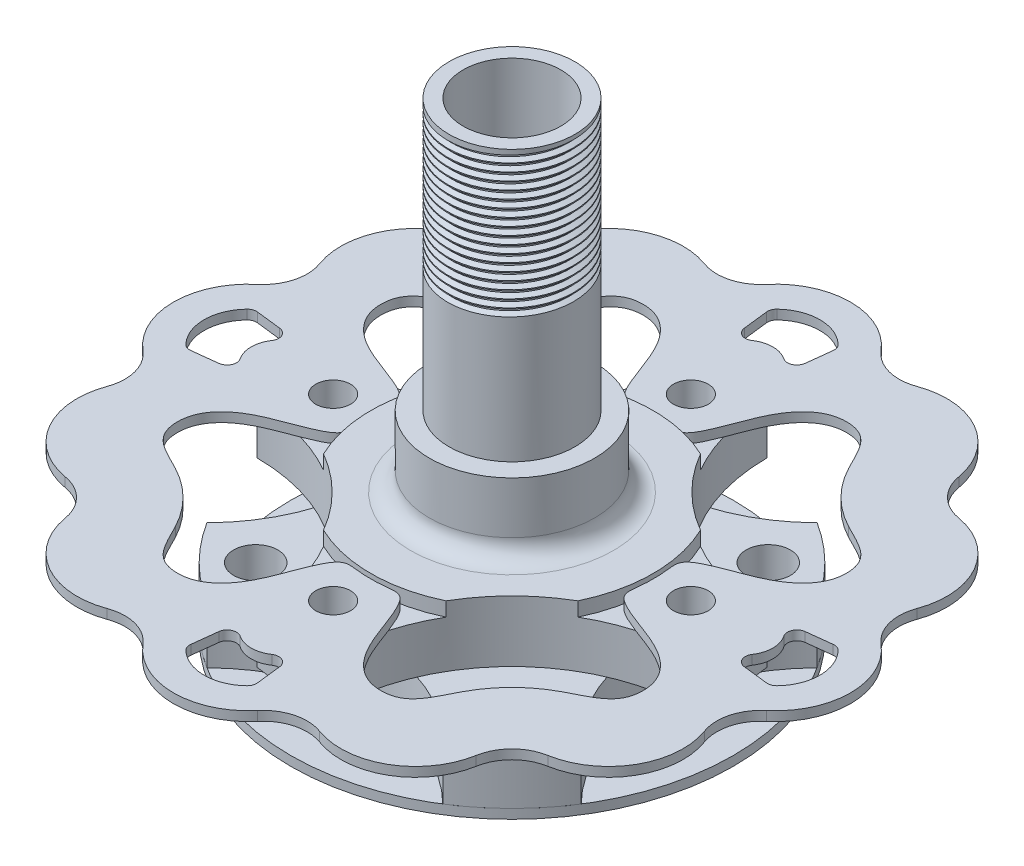
SolidWorks part; units mm, degrees
other "Camera1"
ref_plane "Front Plane" through (0, 0, 0) normal (0, 0, 1) x (1, 0, 0)
ref_plane "Top Plane" through (0, 0, 0) normal (0, 1, 0) x (1, 0, 0)
ref_plane "Right Plane" through (0, 0, 0) normal (1, 0, 0) x (0, 0, -1)
sketch "Sketch1" plane through (0, 0, 0) normal (0, 1, 0) x (1, 0, 0)
  line L0 (-91.3384, 0) -> (0, 0) construction
  line L1 (-79.1014, 45.6692) -> (0, 0) construction
  line L2 (-45.6692, 79.1014) -> (0, 0) construction
  line L3 (0, 91.3384) -> (0, 0) construction
  line L4 (-58.7488, 58.7488) -> (0, 0) construction
  line L5 (-77.6512, 8.9971) -> (-70.888, 8.2135)
  line L9 (0, 91.3384) -> (0, 0) construction
  line L10 (-8.9971, 77.6512) -> (-8.2135, 70.888)
  line L11 (8.9971, 77.6512) -> (8.2135, 70.888)
  line L12 (77.6512, 8.9971) -> (70.888, 8.2135)
  line L13 (0, 91.3384) -> (0, 0) construction
  line L16 (45.6692, 79.1014) -> (0, 0) construction
  line L17 (79.1014, 45.6692) -> (0, 0) construction
  line L18 (91.3384, 0) -> (0, 0) construction
  line L19 (58.7488, 58.7488) -> (0, 0) construction
  line L20 (91.3384, 0) -> (0, 0) construction
  line L23 (0, 91.3384) -> (0, 0) construction
  line L24 (77.6512, -8.9971) -> (70.888, -8.2135)
  line L25 (8.9971, -77.6512) -> (8.2135, -70.888)
  line L26 (-91.3384, 0) -> (0, 0) construction
  line L27 (91.3384, 0) -> (0, 0) construction
  line L28 (77.6512, -8.9971) -> (70.888, -8.2135) [skipped]
  line L30 (-8.9971, -77.6512) -> (-8.2135, -70.888) [skipped]
  line L32 (79.1014, -45.6692) -> (0, 0) construction
  line L33 (45.6692, -79.1014) -> (0, 0) construction
  line L34 (0, -91.3384) -> (0, 0) construction
  line L35 (58.7488, -58.7488) -> (0, 0) construction
  line L36 (0, -91.3384) -> (0, 0) construction
  line L37 (-45.6692, -79.1014) -> (0, 0) construction
  line L38 (-79.1014, -45.6692) -> (0, 0) construction
  line L39 (-58.7488, -58.7488) -> (0, 0) construction
  line L40 (8.9971, 77.6512) -> (8.2135, 70.888) [skipped]
  line L41 (45.6692, 79.1014) -> (0, 0) construction
  line L42 (79.1014, 45.6692) -> (0, 0) construction
  line L43 (58.7488, 58.7488) -> (0, 0) construction
  line L45 (91.3384, 0) -> (0, 0) construction
  line L46 (91.3384, 0) -> (0, 0) construction
  line L47 (79.1014, -45.6692) -> (0, 0) construction
  line L48 (45.6692, -79.1014) -> (0, 0) construction
  line L49 (0, -91.3384) -> (0, 0) construction
  line L50 (58.7488, -58.7488) -> (0, 0) construction
  line L51 (0, -91.3384) -> (0, 0) construction
  line L52 (91.3384, 0) -> (0, 0) construction
  line L53 (-8.9971, -77.6512) -> (-8.2135, -70.888)
  line L54 (-77.6512, -8.9971) -> (-70.888, -8.2135)
  line L55 (0, -91.3384) -> (0, 0) construction
  line L56 (-45.6692, -79.1014) -> (0, 0) construction
  line L57 (-79.1014, -45.6692) -> (0, 0) construction
  line L58 (-91.3384, 0) -> (0, 0) construction
  line L59 (-58.7488, -58.7488) -> (0, 0) construction
  line L60 (-91.3384, 0) -> (0, 0) construction
  line L61 (0, -91.3384) -> (0, 0) construction
  arc A0 (-83.0834, 0) -> (0, 83.0834) centre (0, 0) cw construction
  arc A1 (-91.3384, 0) -> (0, 91.3384) centre (0, 0) cw construction
  arc A2 (-91.3384, 0) -> (-84.1072, 15.4663) centre (-71.1829, 0) cw
  arc A3 (-84.1072, 15.4663) -> (-80.5721, 28.6594) centre (-91.7199, 24.5763) ccw
  arc A4 (-80.5721, 28.6594) -> (-65.1058, 55.4478) centre (-61.6462, 35.5915) cw
  arc A5 (-65.1058, 55.4478) -> (-55.4478, 65.1058) centre (-67.1436, 67.1436) ccw
  arc A6 (-55.4478, 65.1058) -> (-28.6594, 80.5721) centre (-35.5915, 61.6462) cw
  arc A7 (-28.6594, 80.5721) -> (-15.4663, 84.1072) centre (-24.5763, 91.7199) ccw
  arc A8 (-15.4663, 84.1072) -> (0, 91.3384) centre (0, 71.1829) cw
  arc A9 (-61.618, 35.4294) -> (-35.4294, 61.618) centre (-67.1436, 67.1436) ccw
  arc A10 (-38.1, 0) -> (-37.7962, 4.8015) centre (0, 0) cw
  arc A11 (-83.0834, 0) -> (-79.7781, 8.2307) centre (-71.1829, 0) cw
  arc A12 (-69.0761, 4.2678) -> (-70.3834, 0) centre (-62.7634, 0) ccw
  arc A14 (-83.0834, 0) -> (-78.8139, 9.1318) centre (-71.1829, 0) cw construction
  arc A15 (-77.6512, 8.9971) -> (-79.7781, 8.2307) centre (-77.9435, 6.474) ccw
  arc A16 (-69.0761, 4.2678) -> (-70.888, 8.2135) centre (-71.1804, 5.6904) ccw
  circle A17 centre (-48.26, 0) radius 4.699
  arc A29 (0, 38.1) -> (-4.8015, 37.7962) centre (0, 0) ccw
  arc A30 (-4.2678, 69.0761) -> (0, 70.3834) centre (0, 62.7634) cw
  arc A36 (-4.2678, 69.0761) -> (-8.2135, 70.888) centre (-5.6904, 71.1804) cw
  arc A41 (-8.9971, 77.6512) -> (-8.2307, 79.7781) centre (-6.474, 77.9435) cw
  arc A42 (0, 83.0834) -> (-8.2307, 79.7781) centre (0, 71.1829) ccw
  arc A50 (0, 91.3384) -> (15.4663, 84.1072) centre (0, 71.1829) cw
  arc A51 (15.4663, 84.1072) -> (28.6594, 80.5721) centre (24.5763, 91.7199) ccw
  arc A57 (28.6594, 80.5721) -> (55.4478, 65.1058) centre (35.5915, 61.6462) cw
  arc A62 (55.4478, 65.1058) -> (65.1058, 55.4478) centre (67.1436, 67.1436) ccw
  arc A63 (65.1058, 55.4478) -> (80.5721, 28.6594) centre (61.6462, 35.5915) cw
  arc A71 (80.5721, 28.6594) -> (84.1072, 15.4663) centre (91.7199, 24.5763) ccw
  arc A72 (84.1072, 15.4663) -> (91.3384, 0) centre (71.1829, 0) cw
  arc A78 (-38.1, 0) -> (-37.7962, -4.8015) centre (0, 0) ccw
  arc A81 (-69.0761, -4.2678) -> (-70.3834, 0) centre (-62.7634, 0) cw
  arc A83 (35.4294, 61.618) -> (61.618, 35.4294) centre (67.1436, 67.1436) ccw
  arc A84 (0, 38.1) -> (4.8015, 37.7962) centre (0, 0) cw
  arc A85 (91.3384, 0) -> (84.1072, -15.4663) centre (71.1829, 0) cw [skipped]
  arc A86 (84.1072, -15.4663) -> (80.5721, -28.6594) centre (91.7199, -24.5763) ccw [skipped]
  arc A87 (80.5721, -28.6594) -> (65.1058, -55.4478) centre (61.6462, -35.5915) cw [skipped]
  arc A88 (65.1058, -55.4478) -> (55.4478, -65.1058) centre (67.1436, -67.1436) ccw [skipped]
  arc A89 (55.4478, -65.1058) -> (28.6594, -80.5721) centre (35.5915, -61.6462) cw [skipped]
  arc A90 (28.6594, -80.5721) -> (15.4663, -84.1072) centre (24.5763, -91.7199) ccw [skipped]
  arc A91 (15.4663, -84.1072) -> (0, -91.3384) centre (0, -71.1829) cw [skipped]
  arc A92 (61.618, -35.4294) -> (35.4294, -61.618) centre (67.1436, -67.1436) ccw [skipped]
  arc A93 (83.0834, 0) -> (79.7781, -8.2307) centre (71.1829, 0) cw [skipped]
  arc A95 (77.6512, -8.9971) -> (79.7781, -8.2307) centre (77.9435, -6.474) ccw [skipped]
  arc A96 (69.0761, -4.2678) -> (70.888, -8.2135) centre (71.1804, -5.6904) ccw [skipped]
  arc A102 (0, -91.3384) -> (-15.4663, -84.1072) centre (0, -71.1829) cw [skipped]
  arc A103 (-15.4663, -84.1072) -> (-28.6594, -80.5721) centre (-24.5763, -91.7199) ccw [skipped]
  arc A104 (-28.6594, -80.5721) -> (-55.4478, -65.1058) centre (-35.5915, -61.6462) cw [skipped]
  arc A105 (-55.4478, -65.1058) -> (-65.1058, -55.4478) centre (-67.1436, -67.1436) ccw [skipped]
  arc A106 (-65.1058, -55.4478) -> (-80.5721, -28.6594) centre (-61.6462, -35.5915) cw [skipped]
  arc A107 (-80.5721, -28.6594) -> (-84.1072, -15.4663) centre (-91.7199, -24.5763) ccw [skipped]
  arc A108 (-84.1072, -15.4663) -> (-91.3384, 0) centre (-71.1829, 0) cw [skipped]
  arc A109 (-35.4294, -61.618) -> (-61.618, -35.4294) centre (-67.1436, -67.1436) ccw [skipped]
  arc A110 (0, -38.1) -> (-4.8015, -37.7962) centre (0, 0) cw [skipped]
  arc A111 (0, -83.0834) -> (-8.2307, -79.7781) centre (0, -71.1829) cw [skipped]
  arc A112 (-4.2678, -69.0761) -> (0, -70.3834) centre (0, -62.7634) ccw [skipped]
  arc A114 (-8.9971, -77.6512) -> (-8.2307, -79.7781) centre (-6.474, -77.9435) ccw [skipped]
  arc A115 (-4.2678, -69.0761) -> (-8.2135, -70.888) centre (-5.6904, -71.1804) ccw [skipped]
  arc A119 (83.0834, 0) -> (0, -83.0834) centre (0, 0) cw construction
  arc A120 (91.3384, 0) -> (0, -91.3384) centre (0, 0) cw construction
  arc A121 (0, -83.0834) -> (-83.0834, 0) centre (0, 0) cw construction
  arc A122 (0, -91.3384) -> (-91.3384, 0) centre (0, 0) cw construction
  arc A123 (0, 91.3384) -> (15.4663, 84.1072) centre (0, 71.1829) cw [skipped]
  arc A124 (15.4663, 84.1072) -> (28.6594, 80.5721) centre (24.5763, 91.7199) ccw [skipped]
  arc A125 (28.6594, 80.5721) -> (55.4478, 65.1058) centre (35.5915, 61.6462) cw [skipped]
  arc A126 (55.4478, 65.1058) -> (65.1058, 55.4478) centre (67.1436, 67.1436) ccw [skipped]
  arc A127 (65.1058, 55.4478) -> (80.5721, 28.6594) centre (61.6462, 35.5915) cw [skipped]
  arc A128 (80.5721, 28.6594) -> (84.1072, 15.4663) centre (91.7199, 24.5763) ccw [skipped]
  arc A129 (84.1072, 15.4663) -> (91.3384, 0) centre (71.1829, 0) cw [skipped]
  arc A130 (35.4294, 61.618) -> (61.618, 35.4294) centre (67.1436, 67.1436) ccw [skipped]
  arc A131 (0, 38.1) -> (4.8015, 37.7962) centre (0, 0) cw [skipped]
  arc A132 (0, 83.0834) -> (8.2307, 79.7781) centre (0, 71.1829) cw [skipped]
  arc A133 (4.2678, 69.0761) -> (0, 70.3834) centre (0, 62.7634) ccw [skipped]
  arc A135 (8.9971, 77.6512) -> (8.2307, 79.7781) centre (6.474, 77.9435) ccw [skipped]
  arc A136 (4.2678, 69.0761) -> (8.2135, 70.888) centre (5.6904, 71.1804) ccw [skipped]
  arc A137 (0, 91.3384) -> (91.3384, 0) centre (0, 0) cw construction
  arc A138 (0, 83.0834) -> (83.0834, 0) centre (0, 0) cw construction
  arc A144 (38.1, 0) -> (37.7962, -4.8015) centre (0, 0) cw [skipped]
  arc A145 (69.0761, -4.2678) -> (70.3834, 0) centre (62.7634, 0) ccw [skipped]
  arc A146 (0, 83.0834) -> (8.2307, 79.7781) centre (0, 71.1829) cw
  arc A147 (4.2678, 69.0761) -> (0, 70.3834) centre (0, 62.7634) ccw
  arc A148 (8.9971, 77.6512) -> (8.2307, 79.7781) centre (6.474, 77.9435) ccw
  arc A149 (4.2678, 69.0761) -> (8.2135, 70.888) centre (5.6904, 71.1804) ccw
  circle A150 centre (0, 48.26) radius 4.699
  arc A151 (38.1, 0) -> (37.7962, 4.8015) centre (0, 0) ccw
  arc A152 (69.0761, 4.2678) -> (70.3834, 0) centre (62.7634, 0) cw
  arc A153 (69.0761, 4.2678) -> (70.888, 8.2135) centre (71.1804, 5.6904) cw
  arc A154 (77.6512, 8.9971) -> (79.7781, 8.2307) centre (77.9435, 6.474) cw
  arc A155 (83.0834, 0) -> (79.7781, 8.2307) centre (71.1829, 0) ccw
  arc A156 (0, 38.1) -> (-4.8015, 37.7962) centre (0, 0) ccw
  arc A157 (-4.2678, 69.0761) -> (0, 70.3834) centre (0, 62.7634) cw
  arc A158 (0, 83.0834) -> (83.0834, 0) centre (0, 0) cw construction
  arc A159 (0, 91.3384) -> (91.3384, 0) centre (0, 0) cw construction
  arc A160 (91.3384, 0) -> (84.1072, -15.4663) centre (71.1829, 0) cw
  arc A161 (84.1072, -15.4663) -> (80.5721, -28.6594) centre (91.7199, -24.5763) ccw
  arc A162 (80.5721, -28.6594) -> (65.1058, -55.4478) centre (61.6462, -35.5915) cw
  arc A163 (65.1058, -55.4478) -> (55.4478, -65.1058) centre (67.1436, -67.1436) ccw
  arc A164 (55.4478, -65.1058) -> (28.6594, -80.5721) centre (35.5915, -61.6462) cw
  arc A165 (28.6594, -80.5721) -> (15.4663, -84.1072) centre (24.5763, -91.7199) ccw
  arc A166 (15.4663, -84.1072) -> (0, -91.3384) centre (0, -71.1829) cw
  arc A167 (61.618, -35.4294) -> (35.4294, -61.618) centre (67.1436, -67.1436) ccw
  arc A168 (38.1, 0) -> (37.7962, -4.8015) centre (0, 0) cw
  arc A169 (83.0834, 0) -> (79.7781, -8.2307) centre (71.1829, 0) cw
  arc A170 (69.0761, -4.2678) -> (70.3834, 0) centre (62.7634, 0) ccw
  arc A171 (77.6512, -8.9971) -> (79.7781, -8.2307) centre (77.9435, -6.474) ccw
  arc A172 (69.0761, -4.2678) -> (70.888, -8.2135) centre (71.1804, -5.6904) ccw
  circle A173 centre (48.26, 0) radius 4.699
  arc A174 (0, -38.1) -> (4.8015, -37.7962) centre (0, 0) ccw
  arc A175 (4.2678, -69.0761) -> (0, -70.3834) centre (0, -62.7634) cw
  arc A176 (4.2678, -69.0761) -> (8.2135, -70.888) centre (5.6904, -71.1804) cw
  arc A177 (8.9971, -77.6512) -> (8.2307, -79.7781) centre (6.474, -77.9435) cw
  arc A178 (0, -83.0834) -> (8.2307, -79.7781) centre (0, -71.1829) ccw
  arc A179 (38.1, 0) -> (37.7962, 4.8015) centre (0, 0) ccw
  arc A180 (69.0761, 4.2678) -> (70.3834, 0) centre (62.7634, 0) cw
  arc A181 (83.0834, 0) -> (0, -83.0834) centre (0, 0) cw construction
  arc A182 (91.3384, 0) -> (0, -91.3384) centre (0, 0) cw construction
  arc A183 (0, -91.3384) -> (-15.4663, -84.1072) centre (0, -71.1829) cw
  arc A184 (-15.4663, -84.1072) -> (-28.6594, -80.5721) centre (-24.5763, -91.7199) ccw
  arc A185 (-28.6594, -80.5721) -> (-55.4478, -65.1058) centre (-35.5915, -61.6462) cw
  arc A186 (-55.4478, -65.1058) -> (-65.1058, -55.4478) centre (-67.1436, -67.1436) ccw
  arc A187 (-65.1058, -55.4478) -> (-80.5721, -28.6594) centre (-61.6462, -35.5915) cw
  arc A188 (-80.5721, -28.6594) -> (-84.1072, -15.4663) centre (-91.7199, -24.5763) ccw
  arc A189 (-84.1072, -15.4663) -> (-91.3384, 0) centre (-71.1829, 0) cw
  arc A190 (-35.4294, -61.618) -> (-61.618, -35.4294) centre (-67.1436, -67.1436) ccw
  arc A191 (0, -38.1) -> (-4.8015, -37.7962) centre (0, 0) cw
  arc A192 (0, -83.0834) -> (-8.2307, -79.7781) centre (0, -71.1829) cw
  arc A193 (-4.2678, -69.0761) -> (0, -70.3834) centre (0, -62.7634) ccw
  arc A194 (-8.9971, -77.6512) -> (-8.2307, -79.7781) centre (-6.474, -77.9435) ccw
  arc A195 (-4.2678, -69.0761) -> (-8.2135, -70.888) centre (-5.6904, -71.1804) ccw
  circle A196 centre (0, -48.26) radius 4.699
  arc A197 (-38.1, 0) -> (-37.7962, -4.8015) centre (0, 0) ccw
  arc A198 (-69.0761, -4.2678) -> (-70.3834, 0) centre (-62.7634, 0) cw
  arc A199 (-69.0761, -4.2678) -> (-70.888, -8.2135) centre (-71.1804, -5.6904) cw
  arc A200 (-77.6512, -8.9971) -> (-79.7781, -8.2307) centre (-77.9435, -6.474) cw
  arc A201 (-83.0834, 0) -> (-79.7781, -8.2307) centre (-71.1829, 0) ccw
  arc A202 (0, -38.1) -> (4.8015, -37.7962) centre (0, 0) ccw
  arc A203 (4.2678, -69.0761) -> (0, -70.3834) centre (0, -62.7634) cw
  arc A204 (0, -83.0834) -> (-83.0834, 0) centre (0, 0) cw construction
  arc A205 (0, -91.3384) -> (-91.3384, 0) centre (0, 0) cw construction
  spline S0 degree 3 poles (-52.2384, 38.6101) (-57.1023, 36.0693) (-62.2546, 34.2055) (-63.3566, 23.0387) (-56.4818, 14.6017) (-38.7119, 10.4134) (-37.5569, 6.6856) (-37.7962, 4.8015) knots 0 0 0 0 0.284167 0.347787 0.6362 0.911955 1 1 1 1
  spline S1 degree 3 poles (-38.6101, 52.2384) (-36.0693, 57.1023) (-34.2055, 62.2546) (-23.0387, 63.3566) (-14.6017, 56.4818) (-10.4134, 38.7119) (-6.6856, 37.5569) (-4.8015, 37.7962) knots 0 0 0 0 0.284167 0.347787 0.6362 0.911955 1 1 1 1
  spline S2 degree 3 poles (38.6101, 52.2384) (36.0693, 57.1023) (34.2055, 62.2546) (23.0387, 63.3566) (14.6017, 56.4818) (10.4134, 38.7119) (6.6856, 37.5569) (4.8015, 37.7962) knots 0 0 0 0 0.284167 0.347787 0.6362 0.911955 1 1 1 1
  spline S3 degree 3 poles (52.2384, 38.6101) (57.1023, 36.0693) (62.2546, 34.2055) (63.3566, 23.0387) (56.4818, 14.6017) (38.7119, 10.4134) (37.5569, 6.6856) (37.7962, 4.8015) knots 0 0 0 0 0.284167 0.347787 0.6362 0.911955 1 1 1 1
  spline S4 degree 3 poles (52.2384, -38.6101) (57.1023, -36.0693) (62.2546, -34.2055) (63.3566, -23.0387) (56.4818, -14.6017) (38.7119, -10.4134) (37.5569, -6.6856) (37.7962, -4.8015) knots 0 0 0 0 0.284167 0.347787 0.6362 0.911955 1 1 1 1
  spline S5 degree 3 poles (38.6101, -52.2384) (36.0693, -57.1023) (34.2055, -62.2546) (23.0387, -63.3566) (14.6017, -56.4818) (10.4134, -38.7119) (6.6856, -37.5569) (4.8015, -37.7962) knots 0 0 0 0 0.284167 0.347787 0.6362 0.911955 1 1 1 1
  spline S6 degree 3 poles (-38.6101, -52.2384) (-36.0693, -57.1023) (-34.2055, -62.2546) (-23.0387, -63.3566) (-14.6017, -56.4818) (-10.4134, -38.7119) (-6.6856, -37.5569) (-4.8015, -37.7962) knots 0 0 0 0 0.284167 0.347787 0.6362 0.911955 1 1 1 1
  spline S7 degree 3 poles (-52.2384, -38.6101) (-57.1023, -36.0693) (-62.2546, -34.2055) (-63.3566, -23.0387) (-56.4818, -14.6017) (-38.7119, -10.4134) (-37.5569, -6.6856) (-37.7962, -4.8015) knots 0 0 0 0 0.284167 0.347787 0.6362 0.911955 1 1 1 1
  point P26 (0, 0)
  point P27 (-79.1014, 45.6692)
  point P32 (-45.6692, 79.1014)
  point P89 (0, 0)
  point P90 (0, 0)
  point P124 (0, 0)
  point P125 (0, 0)
  point P127 (0, 0)
  point P131 (0, 0)
  point P146 (0, 0)
  point P156 (0, 0)
  point P190 (0, 0)
  point P191 (0, 0)
  point P193 (0, 0)
  point P197 (0, 0)
  point P203 (0, 0)
  point P223 (0, 0)
  point P237 (0, 0)
  point P454 (0, 0)
  point P456 (0, 0)
  point P458 (0, 0)
  point P462 (0, 0)
  point P463 (0, 0)
  dimension "D5" = 10.16
  dimension "D8" = 7.62
  dimension "D11" = 2.54
  dimension "D12" = 2.54
  dimension "D3" = 9.398
  dimension "D7" = 4
  dimension "D2" = 8.255
  dimension "D4" = 20.32
  dimension "D6" = 8.255
  dimension "D13" = 4
extrude "Boss-Extrude2" add sketch "Sketch1" along normal blind 2.54 contours L10 A8 A7 A6 A5 A4 A3 A2 A11 A15 L5 A16 A12 A81 region at (-87.101, 0, -7.4424)
sketch "Sketch4" plane through (0, 0, 0) normal (0, -1, 0) x (1, 0, 0)
  line L0 (-58.858, 9.9314) -> (-58.858, -9.9314) construction
  line L1 (9.9314, 58.858) -> (-9.9314, 58.858) construction
  line L2 (58.858, -9.9314) -> (58.858, 9.9314) construction
  line L3 (-9.9314, -58.858) -> (9.9314, -58.858) construction
  line L4 (-9.9314, 58.858) -> (-58.858, 58.858) construction
  line L5 (-58.858, 58.858) -> (-58.858, 9.9314) construction
  circle A0 centre (0, 0) radius 59.69
  circle A1 centre (0, 0) radius 38.1 construction
  arc A2 (58.858, 9.9314) -> (9.9314, 58.858) centre (58.858, 58.858) cw
  arc A3 (9.9314, -58.858) -> (58.858, -9.9314) centre (58.858, -58.858) cw
  arc A4 (4.8015, 37.7962) -> (-4.8015, 37.7962) centre (0, 0) ccw construction
  arc A5 (-9.9314, 58.858) -> (-58.858, 9.9314) centre (-58.858, 58.858) cw
  arc A6 (-58.858, -9.9314) -> (-9.9314, -58.858) centre (-58.858, -58.858) cw
  circle A15 centre (48.26, 0) radius 4.699 construction
  circle A16 centre (0, -48.26) radius 4.699 construction
  circle A17 centre (-48.26, 0) radius 4.699 construction
  circle A18 centre (0, 48.26) radius 4.699 construction
  circle A19 centre (48.26, 0) radius 4.699
  circle A20 centre (0, -48.26) radius 4.699
  circle A21 centre (-48.26, 0) radius 4.699
  circle A22 centre (0, 48.26) radius 4.699
  point P9 (-58.858, 0)
  point P12 (0, 58.858)
  point P19 (0, 0)
  point P31 (0, 0)
  dimension "D1" = 119.38
  dimension "D2" = 19.8628
  dimension "D4" = 90
  dimension "D3" = 4
  dimension "D5" = 4
extrude "Boss-Extrude3" add sketch "Sketch4" along normal blind 12.7 contours A0 A6 A3 A2 A5 A22 A21 A20 A19 region at (0, 0, 0)
sketch "Sketch5" plane through (0, -12.7, 0) normal (0, -1, 0) x (1, 0, 0)
  circle A4 centre (34.574, -34.574) radius 5.969
  circle A5 centre (34.574, 34.574) radius 5.969
  circle A6 centre (-34.574, 34.574) radius 5.969
  circle A7 centre (-34.574, -34.574) radius 5.969
  arc A16 (-50.5004, -31.8215) -> (-31.8215, -50.5004) centre (0, 0) ccw
  arc A17 (31.8215, -50.5004) -> (-31.8215, -50.5004) centre (0, -82.3219) ccw
  arc A18 (31.8215, -50.5004) -> (50.5004, -31.8215) centre (0, 0) ccw
  arc A19 (50.5004, 31.8215) -> (50.5004, -31.8215) centre (82.3219, 0) ccw
  arc A20 (50.5004, 31.8215) -> (31.8215, 50.5004) centre (0, 0) ccw
  arc A21 (-31.8215, 50.5004) -> (31.8215, 50.5004) centre (0, 82.3219) ccw
  arc A22 (-31.8215, 50.5004) -> (-50.5004, 31.8215) centre (0, 0) ccw
  arc A23 (-50.5004, -31.8215) -> (-50.5004, 31.8215) centre (-82.3219, 0) ccw
extrude "Boss-Extrude4" add sketch "Sketch5" along normal blind 15.24 separate body
sketch "Sketch6" plane through (0, -27.94, 0) normal (0, -1, 0) x (1, 0, 0)
  circle A0 centre (0, 0) radius 59.69
  circle A1 centre (0, 0) radius 25.4
  arc A2 (58.858, -9.9314) -> (58.858, 9.9314) centre (0, 0) ccw construction
  circle A3 centre (-34.574, -34.574) radius 5.969 construction
  circle A4 centre (34.574, -34.574) radius 5.969 construction
  circle A5 centre (34.574, 34.574) radius 5.969 construction
  circle A6 centre (-34.574, 34.574) radius 5.969 construction
  circle A7 centre (-34.574, -34.574) radius 5.969
  circle A8 centre (34.574, -34.574) radius 5.969
  circle A9 centre (34.574, 34.574) radius 5.969
  circle A10 centre (-34.574, 34.574) radius 5.969
  dimension "D1" = 50.8
extrude "Boss-Extrude5" add sketch "Sketch6" along normal blind 2.54 separate body
sketch "Sketch7" plane through (0, 0, 0) normal (0, 1, 0) x (1, 0, 0)
  circle A0 centre (0, 0) radius 38.1
  arc A1 (-37.7962, 4.8015) -> (-37.7962, -4.8015) centre (0, 0) ccw construction
  arc A11 (-45.2034, 11.8754) -> (-11.8754, 45.2034) centre (-58.858, 58.858) ccw
  arc A12 (-37.7962, 4.8015) -> (-37.7962, -4.8015) centre (0, 0) ccw
  arc A13 (-11.8754, -45.2034) -> (-45.2034, -11.8754) centre (-58.858, -58.858) ccw
  arc A15 (45.2034, -11.8754) -> (11.8754, -45.2034) centre (58.858, -58.858) ccw
  arc A17 (11.8754, 45.2034) -> (45.2034, 11.8754) centre (58.858, 58.858) ccw
  arc A19 (-34.3305, 16.5234) -> (-16.5234, 34.3305) centre (-58.858, 58.858) ccw
  arc A20 (-37.7962, 4.8015) -> (-37.7962, -4.8015) centre (0, 0) ccw
  arc A21 (-16.5234, -34.3305) -> (-34.3305, -16.5234) centre (-58.858, -58.858) ccw
  arc A23 (34.3305, -16.5234) -> (16.5234, -34.3305) centre (58.858, -58.858) ccw
  arc A25 (16.5234, 34.3305) -> (34.3305, 16.5234) centre (58.858, 58.858) ccw
  arc A26 (4.8015, 37.7962) -> (-4.8015, 37.7962) centre (0, 0) ccw
  arc A27 (4.8015, 37.7962) -> (-4.8015, 37.7962) centre (0, 0) ccw
  arc A28 (-4.8015, -37.7962) -> (4.8015, -37.7962) centre (0, 0) ccw
  arc A29 (-4.8015, -37.7962) -> (4.8015, -37.7962) centre (0, 0) ccw
  arc A30 (37.7962, -4.8015) -> (37.7962, 4.8015) centre (0, 0) ccw
  arc A31 (37.7962, -4.8015) -> (37.7962, 4.8015) centre (0, 0) ccw
  spline S8 degree 3 poles (985.11, 179.4636) (16.6678, 75.4373) (-30.7541, -51.6233) (-10.7239, 245.8028) (-335.8105, -900.8735) knots -0.031783 -0.031783 -0.031783 -0.031783 0.862417 2.501127 2.501127 2.501127 2.501127 only from (-4.8015, 37.7962) to (-11.8754, 45.2034)
  spline S9 degree 3 poles (900.8755, 335.8111) (-245.803, 10.7239) (51.6226, 30.7541) (-75.4367, -16.6676) (-179.4615, -985.0902) knots -0.726756 -0.726756 -0.726756 -0.726756 0.911955 1.806148 1.806148 1.806148 1.806148 only from (-45.2034, 11.8754) to (-37.7962, 4.8015)
  spline S10 degree 3 poles (-4.8015, 37.7962) (-6.6856, 37.5569) (-8.9976, 38.2732) (-10.7743, 42.3579) (-11.8754, 45.2034) knots 0.774372 0.774372 0.774372 0.774372 0.862417 1 1 1 1
  spline S11 degree 3 poles (-179.4636, 985.11) (-75.4373, 16.6678) (51.6233, -30.7541) (-245.8028, -10.7239) (900.8735, -335.8105) knots -0.031783 -0.031783 -0.031783 -0.031783 0.862417 2.501127 2.501127 2.501127 2.501127 only from (-37.7962, -4.8015) to (-45.2034, -11.8754)
  spline S12 degree 3 poles (-37.7962, -4.8015) (-37.5569, -6.6856) (-38.2732, -8.9976) (-42.3579, -10.7743) (-45.2034, -11.8754) knots 0.774372 0.774372 0.774372 0.774372 0.862417 1 1 1 1
  spline S13 degree 3 poles (-335.8111, 900.8755) (-10.7239, -245.803) (-30.7541, 51.6226) (16.6676, -75.4367) (985.0902, -179.4615) knots -0.726756 -0.726756 -0.726756 -0.726756 0.911955 1.806148 1.806148 1.806148 1.806148 only from (-11.8754, -45.2034) to (-4.8015, -37.7962)
  spline S14 degree 3 poles (-11.8754, -45.2034) (-10.7743, -42.3579) (-8.9976, -38.2732) (-6.6856, -37.5569) (-4.8015, -37.7962) knots 0.774372 0.774372 0.774372 0.774372 0.911955 1 1 1 1
  spline S15 degree 3 poles (-985.11, -179.4636) (-16.6678, -75.4373) (30.7541, 51.6233) (10.7239, -245.8028) (335.8105, 900.8735) knots -0.031783 -0.031783 -0.031783 -0.031783 0.862417 2.501127 2.501127 2.501127 2.501127 only from (4.8015, -37.7962) to (11.8754, -45.2034)
  spline S16 degree 3 poles (4.8015, -37.7962) (6.6856, -37.5569) (8.9976, -38.2732) (10.7743, -42.3579) (11.8754, -45.2034) knots 0.774372 0.774372 0.774372 0.774372 0.862417 1 1 1 1
  spline S17 degree 3 poles (-900.8755, -335.8111) (245.803, -10.7239) (-51.6226, -30.7541) (75.4367, 16.6676) (179.4615, 985.0902) knots -0.726756 -0.726756 -0.726756 -0.726756 0.911955 1.806148 1.806148 1.806148 1.806148 only from (45.2034, -11.8754) to (37.7962, -4.8015)
  spline S18 degree 3 poles (45.2034, -11.8754) (42.3579, -10.7743) (38.2732, -8.9976) (37.5569, -6.6856) (37.7962, -4.8015) knots 0.774372 0.774372 0.774372 0.774372 0.911955 1 1 1 1
  spline S19 degree 3 poles (179.4636, -985.11) (75.4373, -16.6678) (-51.6233, 30.7541) (245.8028, 10.7239) (-900.8735, 335.8105) knots -0.031783 -0.031783 -0.031783 -0.031783 0.862417 2.501127 2.501127 2.501127 2.501127 only from (37.7962, 4.8015) to (45.2034, 11.8754)
  spline S20 degree 3 poles (37.7962, 4.8015) (37.5569, 6.6856) (38.2732, 8.9976) (42.3579, 10.7743) (45.2034, 11.8754) knots 0.774372 0.774372 0.774372 0.774372 0.862417 1 1 1 1
  spline S21 degree 3 poles (335.8111, -900.8755) (10.7239, 245.803) (30.7541, -51.6226) (-16.6676, 75.4367) (-985.0902, 179.4615) knots -0.726756 -0.726756 -0.726756 -0.726756 0.911955 1.806148 1.806148 1.806148 1.806148 only from (11.8754, 45.2034) to (4.8015, 37.7962)
  spline S22 degree 3 poles (11.8754, 45.2034) (10.7743, 42.3579) (8.9976, 38.2732) (6.6856, 37.5569) (4.8015, 37.7962) knots 0.774372 0.774372 0.774372 0.774372 0.911955 1 1 1 1
  arc M20 (-11.8754, 45.2034) -> (-45.2034, 11.8754) centre (-58.858, 58.858) cw
  arc M22 (-37.7962, 4.8015) -> (-37.7962, -4.8015) centre (0, 0) ccw
  arc M24 (-45.2034, -11.8754) -> (-11.8754, -45.2034) centre (-58.858, -58.858) cw
  arc M28 (11.8754, -45.2034) -> (45.2034, -11.8754) centre (58.858, -58.858) cw
  arc M32 (45.2034, 11.8754) -> (11.8754, 45.2034) centre (58.858, 58.858) cw
  dimension "D1" = 0
extrude "Boss-Extrude7" add sketch "Sketch7" along normal blind 3.81 contours A0 M28 M32 M20 M22 M24 region at (0, 0, 0)
sketch "Sketch8" plane through (0, 3.81, 0) normal (0, 1, 0) x (1, 0, 0)
  circle A0 centre (0, 0) radius 22.3012
  dimension "D1" = 44.6024
extrude "Boss-Extrude8" add sketch "Sketch8" along normal blind 19.05
sketch "Sketch9" plane through (0, 22.86, 0) normal (0, 1, 0) x (1, 0, 0)
  circle A0 centre (0, 0) radius 16.9926
  dimension "D1" = 33.9852
extrude "Boss-Extrude9" add sketch "Sketch9" along normal blind 73.025 separate body
sketch "Sketch10" plane through (0, 95.885, 0) normal (0, 1, 0) x (1, 0, 0)
  circle A2 centre (0, 0) radius 13.1826
  circle A3 centre (0, 0) radius 13.1826
  dimension "D1" = 3.81
extrude "Cut-Extrude1" cut sketch "Sketch10" against normal through all both and the other way through all
thread "Thread1" pitch 2.1167 method cut profile "Thread Profile1" start angle 0, offset 0, length 38.1, pitch 2.1167, diameter 33.9852
ref_plane "Plane1" through (-16.9926, 95.885, 0) normal (0, 0, 1) x (-1, 0, 0)
sketch "Thread Profile1" plane through (-16.9926, 95.885, 0) normal (0, 0, 1) x (-1, 0, 0)
  line L0 (0, 0) -> (0, 2.1167) construction
  line L11 (0, 0) -> (0, 1.8521)
  line L12 (0, 1.8521) -> (-1.1457, 1.1906)
  line L13 (-1.1457, 1.1906) -> (-1.1457, 0.6615)
  line L15 (-1.1457, 0.6615) -> (0, 0)
  line L17 (-1.1457, 0.926) -> (0, 0.926) construction
  point P2 (0, 0)
  dimension "Pitch" = 2.1167
  dimension "Profile_Angle" = 60
  dimension "Profile_Land" = 0.5292
  dimension "Profile_Height" = 1.1457
fillet "Fillet2" radius 5.08 1 edges at (0, 3.81, 22.3012)
